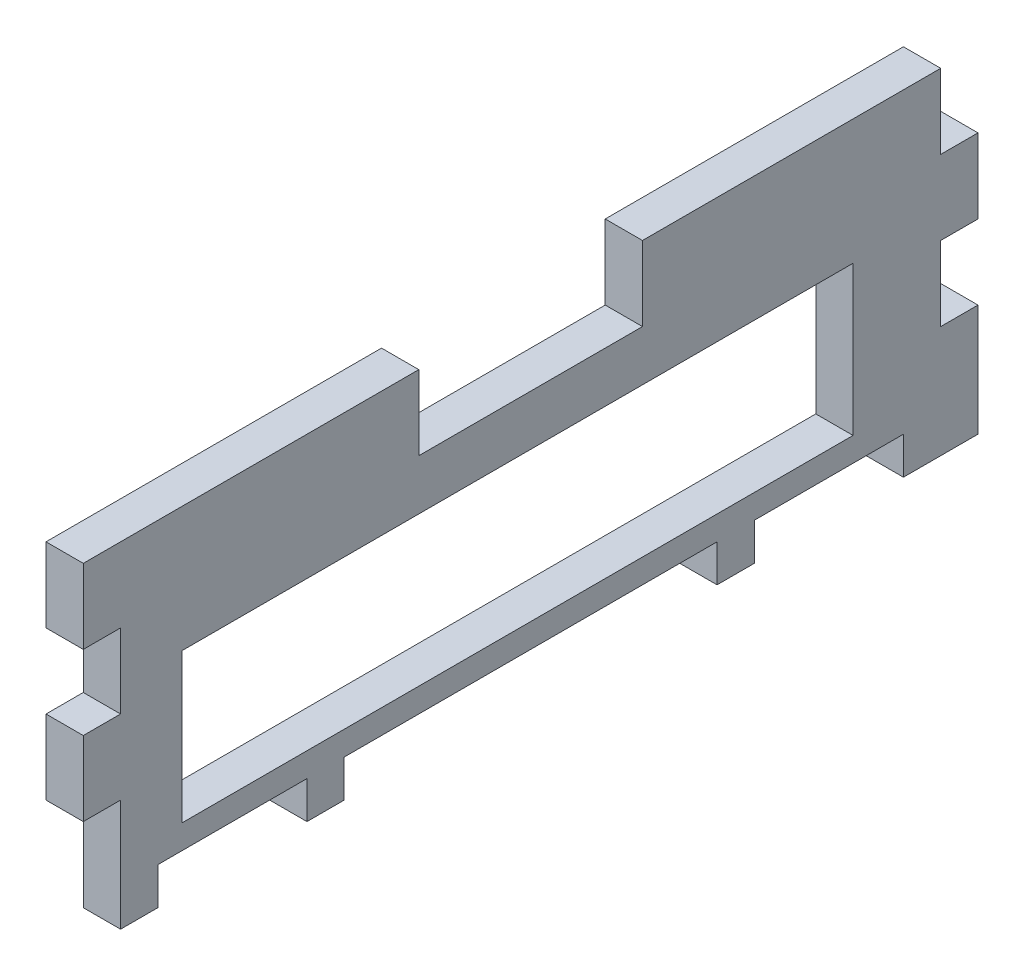
SolidWorks part; units mm, degrees
ref_plane "Front Plane" through (0, 0, 0) normal (0, 0, 1) x (1, 0, 0)
ref_plane "Top Plane" through (0, 0, 0) normal (0, 1, 0) x (1, 0, 0)
ref_plane "Right Plane" through (0, 0, 0) normal (1, 0, 0) x (0, 0, -1)
sketch "Sketch1" plane through (0, 0, 0) normal (1, 0, 0) x (0, 0, -1)
  line L0 (-76.2, 12.7) -> (-69.85, 12.7)
  line L1 (-76.2, -25.4) -> (76.2, -25.4)
  line L2 (-76.2, -25.4) -> (-76.2, 25.4)
  line L3 (-76.2, 25.4) -> (76.2, 25.4)
  line L4 (76.2, -25.4) -> (76.2, 25.4)
  line L5 (-76.2, -25.4) -> (76.2, 25.4) construction
  line L6 (-76.2, 25.4) -> (76.2, -25.4) construction
  line L7 (-69.85, 12.7) -> (-69.85, 0)
  line L8 (-69.85, 0) -> (-76.2, 0)
  line L9 (-76.2, 0) -> (-76.2, -12.7)
  line L10 (-76.2, -12.7) -> (-69.85, -12.7)
  line L11 (-69.85, -12.7) -> (-69.85, -25.4)
  line L12 (0, 25.4) -> (0, -25.4) construction
  line L13 (-69.85, -25.4) -> (-69.85, -21.2928)
  line L14 (38.1, -31.75) -> (31.75, -31.75)
  line L15 (-69.85, -25.4) -> (-63.5, -25.4)
  line L16 (-63.5, -25.4) -> (-38.1, -25.4)
  line L17 (-38.1, -25.4) -> (-38.1, -31.75)
  line L18 (-38.1, -31.75) -> (-31.75, -31.75)
  line L19 (-31.75, -31.75) -> (-31.75, -25.4)
  line L20 (-69.85, -25.4) -> (-69.85, -31.75)
  line L21 (-69.85, -31.75) -> (-63.5, -31.75)
  line L22 (-63.5, -25.4) -> (-63.5, -31.75)
  line L23 (31.75, -31.75) -> (31.75, -25.4)
  line L24 (38.1, -25.4) -> (38.1, -31.75)
  line L25 (63.5, -25.4) -> (63.5, -31.75)
  line L26 (69.85, -31.75) -> (63.5, -31.75)
  line L27 (69.85, -25.4) -> (69.85, -31.75)
  line L28 (69.85, -12.7) -> (69.85, -25.4)
  line L29 (76.2, -12.7) -> (69.85, -12.7)
  line L30 (69.85, 0) -> (76.2, 0)
  line L31 (76.2, 12.7) -> (69.85, 12.7)
  line L32 (69.85, 12.7) -> (69.85, 0)
  line L33 (69.85, 12.7) -> (69.85, 25.4)
  line L34 (69.85, 25.4) -> (69.85, 0)
  line L35 (69.85, -12.7) -> (69.85, 0)
  line L36 (76.2, -25.4) -> (76.2, -31.75)
  line L37 (-19.05, 38.1) -> (19.05, 38.1)
  line L38 (-19.05, 38.1) -> (-19.05, 12.7)
  line L39 (-19.05, 12.7) -> (19.05, 12.7)
  line L40 (19.05, 38.1) -> (19.05, 12.7)
  line L41 (-19.05, 38.1) -> (19.05, 12.7) construction
  line L42 (-19.05, 12.7) -> (19.05, 38.1) construction
  line L43 (76.2, -31.75) -> (69.85, -31.75)
  line L45 (-59.3817, 4.1072) -> (54.9183, 4.1072)
  line L46 (-59.3817, 4.1072) -> (-59.3817, -21.2928)
  line L47 (-59.3817, -21.2928) -> (54.9183, -21.2928)
  line L48 (54.9183, 4.1072) -> (54.9183, -21.2928)
  point P0 (0, 0)
  dimension "D1" = 6.35
  dimension "D2" = 12.7
  dimension "D3" = 12.7
  dimension "D4" = 25.4
extrude "Boss-Extrude1" add sketch "Sketch1" along normal blind 6.35 contours L28 L35 L32 L33 L3 L2 L0 L7 L8 L10 L11 L1 | L31 L32 L30 L4 | L4 L29 L28 L1 | L27 L1 L25 L26 | L24 L1 L23 L14 | L18 L19 L1 L17 | L22 L1 L20 L21 region at (0, 4.3279, 1.3689) region at (0, -28.575, 66.675) region at (0, 6.35, -73.025) region at (0, -28.575, 34.925) region at (0, -19.05, -73.025) region at (0, -28.575, -34.925) region at (0, -28.575, -66.675)
extrude "Boss-Extrude2" add sketch "Sketch1<4>" along normal blind 6.35 contours L43 L36 L1 L27 region at (0, -28.575, -73.025)
sketch "Sketch1<4>" plane through (0, 0, 0) normal (1, 0, 0) x (0, 0, -1) same geometry as "Sketch1"
